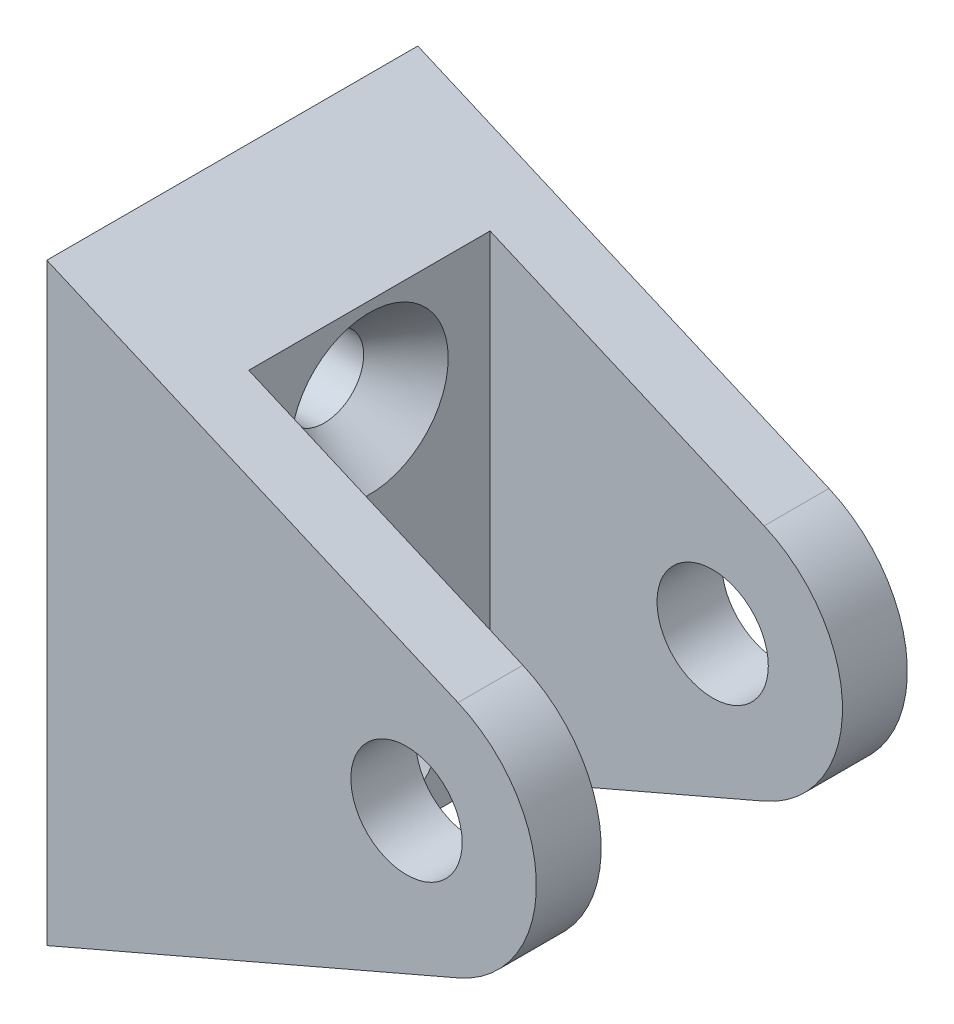
SolidWorks part; units mm, degrees
ref_plane "Front Plane" through (0, 0, 0) normal (0, 0, 1) x (1, 0, 0)
ref_plane "Top Plane" through (0, 0, 0) normal (0, 1, 0) x (1, 0, 0)
ref_plane "Right Plane" through (0, 0, 0) normal (1, 0, 0) x (0, 0, -1)
sketch "Sketch1" plane through (0, 0, 0) normal (0, 1, 0) x (1, 0, 0)
  line L0 (0, 0) -> (43.4837, 0)
  line L1 (43.4837, 0) -> (43.4837, 5.5499)
  line L2 (43.4837, 5.5499) -> (11.7337, 5.5499)
  line L3 (11.7337, 5.5499) -> (11.7337, 26.2001)
  line L4 (11.7337, 26.2001) -> (43.4837, 26.2001)
  line L5 (43.4837, 26.2001) -> (43.4837, 31.75)
  line L6 (43.4837, 31.75) -> (0, 31.75)
  line L7 (0, 31.75) -> (0, 0)
  line L8 (30.7837, 31.75) -> (30.7837, 0) construction
  circle A0 centre (30.7837, 15.875) radius 10.3505 construction
  dimension "D4" = 20.701
  dimension "D1" = 31.75
  dimension "D2" = 31.75
  dimension "D3" = 20.6502
  dimension "D5" = 12.7
extrude "Camber Block Extrude" add sketch "Sketch1" along normal blind 50.8
sketch "Sketch2" plane through (11.7337, 0, 0) normal (1, 0, 0) x (0, 0, -1)
  line L0 (5.5499, 25.4) -> (26.2001, 25.4) construction
  line L1 (5.5499, 50.8) -> (5.5499, 0) construction
  line L2 (26.2001, 50.8) -> (26.2001, 0) construction
  line L3 (15.875, 38.1) -> (15.875, 12.7) construction
  circle A0 centre (15.875, 38.1) radius 3.175 construction
  circle A1 centre (15.875, 12.7) radius 3.175 construction
  point P6 (15.875, 38.1)
  point P7 (15.875, 12.7)
  point P10 (15.875, 25.4)
  point P12 (15.875, 25.4)
  point P17 (15.875, 38.1)
  point P19 (15.875, 12.7)
  dimension "D2" = 6.35
  dimension "D3" = 6.35
  dimension "D1" = 25.4
hole_wizard "CSK for 1/4 Flat Head Machine Screw (100)1" positions "Sketch2" profile "Sketch3" countersink size "1/4" standard "ANSI Inch" end condition through all
sketch "Sketch3" plane through (11.7337, 12.7, -15.875) normal (0, 1, 0) x (0, 0, -1)
  line L0 (0, 0) -> (0, 11.7337)
  line L1 (0, 11.7337) -> (3.3782, 11.7337)
  line L2 (3.3782, 11.7337) -> (3.3782, 3.8716)
  line L3 (3.3782, 3.8716) -> (6.7437, 0)
  line L5 (6.7437, 0) -> (0, 0)
  line L6 (-3.3782, 3.8716) -> (-6.7437, 0) construction
  line L11 (0, -6.35) -> (0, 107.95) construction
  dimension "Thru Hole Dia." = 6.7564
  dimension "Thru Hole Depth" = 11.7337
  dimension "Near C'Sink Dia." = 13.4874
  dimension "Near C'Sink Angle" = 82
sketch "Sketch5" plane through (0, 0, 0) normal (0, 0, 1) x (1, 0, 0)
  line L0 (0, 25.4) -> (43.4837, 25.4) construction
  line L1 (0, 50.8) -> (0, 0) construction
  line L2 (43.4837, 50.8) -> (43.4837, 0) construction
  line L3 (0, 0) -> (35.1898, 15.1983)
  line L4 (0, 50.8) -> (35.1898, 35.6017)
  line L5 (0, 0) -> (43.4837, 0)
  line L6 (43.4837, 0) -> (43.4837, 50.8)
  line L7 (43.4837, 50.8) -> (0, 50.8)
  circle A0 centre (30.7837, 25.4) radius 4.7625
  arc A1 (35.1898, 15.1983) -> (35.1898, 35.6017) centre (30.7837, 25.4) ccw
  dimension "D1" = 9.525
  dimension "D2" = 6.35
extrude "Cut-Extrude1" cut sketch "Sketch5" against normal up to surface (31.75 mm away) up to face at (21.7418, 25.4, -31.75)
